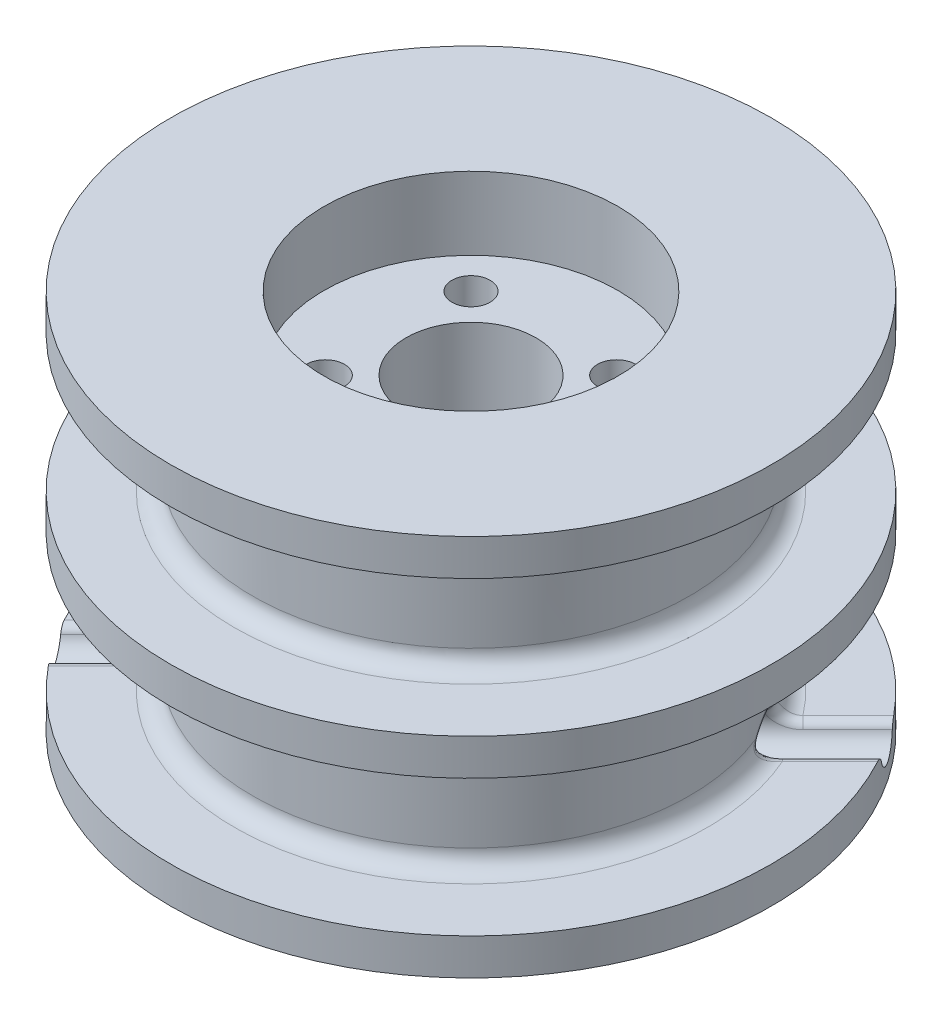
SolidWorks part; units mm, degrees
material "ABS"
ref_plane "前视基准面" through (0, 0, 0) normal (0, 0, 1) x (1, 0, 0)
ref_plane "上视基准面" through (0, 0, 0) normal (0, 1, 0) x (1, 0, 0)
ref_plane "右视基准面" through (0, 0, 0) normal (1, 0, 0) x (0, 0, -1)
other "Configuration Table"
sketch "草图1" plane through (0, 0, 0) normal (1, 0, 0) x (0, 0, -1)
  line L0 (0, 0) -> (0, 55.9155) construction
  line L1 (-7.15, 34) -> (-16.15, 34)
  line L2 (-16.15, 34) -> (-16.15, 42)
  line L3 (-16.15, 42) -> (-33, 42)
  line L4 (-33, 42) -> (-33, 38)
  line L5 (-33, 38) -> (-24, 38)
  line L6 (-24, 38) -> (-24, 23)
  line L7 (-24, 23) -> (-33, 23)
  line L8 (-33, 23) -> (-33, 19)
  line L9 (-33, 19) -> (-24, 19)
  line L10 (-24, 19) -> (-24, 4)
  line L11 (-24, 4) -> (-33, 4)
  line L12 (-33, 4) -> (-33, 0)
  line L13 (-33, 0) -> (-16.15, 0)
  line L14 (0, 0) -> (0, 34) construction
  line L15 (-16.15, 0) -> (-16.15, 8)
  line L16 (-16.15, 8) -> (-7.15, 8)
  line L17 (-16.15, 0) -> (0, 0) construction
  line L18 (-7.15, 34) -> (-7.15, 8)
  dimension "D1" = 4
  dimension "D2" = 4
  dimension "D3" = 4
  dimension "D4" = 15
  dimension "D5" = 33
  dimension "D6" = 33
  dimension "D7" = 33
  dimension "D8" = 15
  dimension "D9" = 24
  dimension "D10" = 24
  dimension "D11" = 16.15
  dimension "D12" = 8
  dimension "D13" = 8
  dimension "D14" = 16.15
  dimension "D15" = 7.15
  dimension "D16" = 16.15
revolve "旋转1" add sketch "草图1" angle 360 about L0
sketch "草图2" plane through (0, 34, 0) normal (0, 1, 0) x (1, 0, 0)
  line L1 (8, -8) -> (-8, -8) construction
  line L2 (8, -8) -> (8, 8) construction
  line L3 (8, 8) -> (-8, 8) construction
  line L4 (-8, -8) -> (-8, 8) construction
  line L5 (8, -8) -> (-8, 8) construction
  line L6 (8, 8) -> (-8, -8) construction
  circle A0 centre (-8, 8) radius 2.1
  circle A1 centre (8, 8) radius 2.1
  circle A2 centre (8, -8) radius 2.1
  circle A3 centre (-8, -8) radius 2.1
  point P0 (0, 0)
  dimension "D2" = 4.2
  dimension "D1" = 16
extrude "切除-拉伸1" cut sketch "草图2" against normal through all
fillet "圆角1" radius 2 4 edges at (0, 19, -24) (0, 4, -24) (0, 38, -24) (0, 23, -24)
ref_axis "基准轴2" through (0, 15, 0) along (0, -1, 0)
ref_plane "基准面1" through (28.2843, 0, -28.2843) normal (0.7071, 0, -0.7071) x (-0.7071, 0, -0.7071)
sketch "草图3" plane through (28.2843, 0, -28.2843) normal (0.7071, 0, -0.7071) x (-0.7071, 0, -0.7071)
  line L1 (-4.6785, 4) -> (-5.5445, 5.5) construction
  line L2 (-5.5445, 5.5) -> (-7.2766, 5.5) construction
  line L3 (-7.2766, 5.5) -> (-8.1426, 4) construction
  line L4 (-8.1426, 4) -> (-7.2766, 2.5) construction
  line L5 (-7.2766, 2.5) -> (-5.5445, 2.5) construction
  line L6 (-5.5445, 2.5) -> (-4.6785, 4) construction
  arc A1 (-3.9357, 1.5251) -> (-8.8854, 6.4749) centre (-6.4106, 4) ccw construction
  circle A2 centre (-6.4106, 4) radius 2.25
  circle A3 centre (-6.4106, 4) radius 1.5 construction
  dimension "D1" = 4.5
  dimension "D2" = 3
extrude "切除-拉伸2" cut sketch "草图3" against normal blind 30
pattern_circular "阵列(圆周)1" count 2 over 360 about axis through (0, 0, 0) along (0, -1, 0) of "切除-拉伸2" reverse direction yes
fillet "圆角2" radius 1 10 edges at (-23.59, 4, 17.7061) (-26.0497, 4, 13.8018) (-19.9845, 4.9964, 13.7715) (-22.2082, 4.7742, 10.1546) (-21.0295, 6.2323, 11.5654) (23.59, 4, -17.7061) (19.9845, 4.9964, -13.7715) (21.0295, 6.2323, -11.5654) (22.2082, 4.7742, -10.1546) (26.0497, 4, -13.8018)
